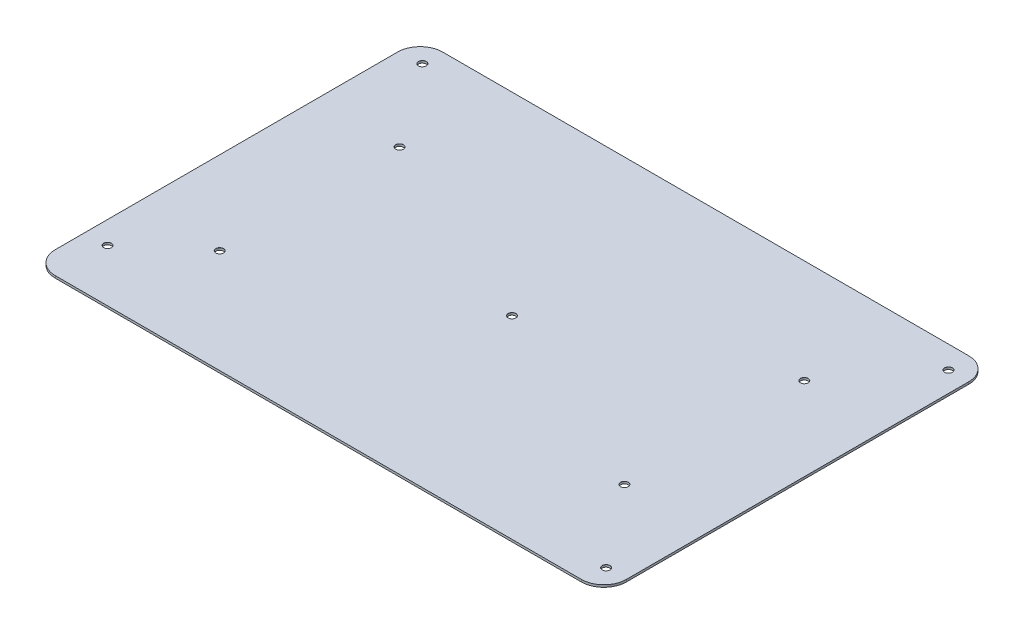
SolidWorks part; units mm, degrees
ref_plane "Front Plane" through (0, 0, 0) normal (0, 0, 1) x (1, 0, 0)
ref_plane "Top Plane" through (0, 0, 0) normal (0, 1, 0) x (1, 0, 0)
ref_plane "Right Plane" through (0, 0, 0) normal (1, 0, 0) x (0, 0, -1)
sketch "Sketch1" plane through (0, 0, 0) normal (0, 1, 0) x (1, 0, 0)
  line L1 (-127, 86.135) -> (127, 86.135)
  line L2 (-127, 86.135) -> (-127, -86.135)
  line L3 (-127, -86.135) -> (127, -86.135)
  line L4 (127, 86.135) -> (127, -86.135)
  line L5 (-127, 86.135) -> (127, -86.135) construction
  line L6 (-127, -86.135) -> (127, 86.135) construction
  point P0 (0, 0)
  dimension "D1" = 254
  dimension "D2" = 172.27
extrude "Boss-Extrude1" add sketch "Sketch1" along normal blind 1
fillet "Fillet1" radius 10 4 edges at (-127, 0.5, 86.135) (127, 0.5, 86.135) (127, 0.5, -86.135) (-127, 0.5, -86.135)
hole_wizard "M3 Clearance Hole1" positions "Sketch2" profile "Sketch3" hole size "M3" standard "ANSI Metric" end condition through all
sketch "Sketch2" plane through (0, 1, 0) normal (0, 1, 0) x (1, 0, 0)
  line L1 (-90, 40) -> (90, 40)
  line L2 (-90, 40) -> (-90, -40)
  line L3 (-90, -40) -> (90, -40)
  line L4 (90, 40) -> (90, -40)
  line L5 (-90, 40) -> (90, -40) construction
  line L6 (-90, -40) -> (90, 40) construction
  line L7 (117, 86.135) -> (-117, 86.135) construction
  line L8 (-127, 76.135) -> (-127, -76.135) construction
  line L9 (-117, -86.135) -> (117, -86.135) construction
  line L10 (127, -76.135) -> (127, 76.135) construction
  point P0 (-117, 77.135)
  point P2 (-117, -62.865)
  point P4 (118, -76.135)
  point P6 (118, 76.135)
  point P8 (-90, -40)
  point P10 (90, -40)
  point P13 (-90, 40)
  point P15 (90, 40)
  point P128 (0, 0)
  point P139 (0, 0)
  point P141 (0, 0)
  dimension "D1" = 180
  dimension "D2" = 80
  dimension "D3" = 9
  dimension "D4" = 10
  dimension "D5" = 10
  dimension "D6" = 23.27
  dimension "D7" = 10
  dimension "D8" = 9
  dimension "D9" = 9
  dimension "D10" = 10
sketch "Sketch3" plane through (-117, 1, -77.135) normal (1, 0, 0) x (0, 0, 1)
  line L0 (0, 0) -> (0, 1)
  line L1 (0, 1) -> (1.7, 1)
  line L2 (1.7, 1) -> (1.7, 0.025)
  line L3 (1.7, 0.025) -> (1.725, 0)
  line L5 (1.725, 0) -> (0, 0)
  line L6 (-1.7, 0.025) -> (-1.725, 0) construction
  line L11 (0, -6.35) -> (0, 107.95) construction
  dimension "Thru Hole Dia." = 3.4
  dimension "Thru Hole Depth" = 1
  dimension "Near C'Sink Dia." = 3.45
  dimension "Near C'Sink Angle" = 90
